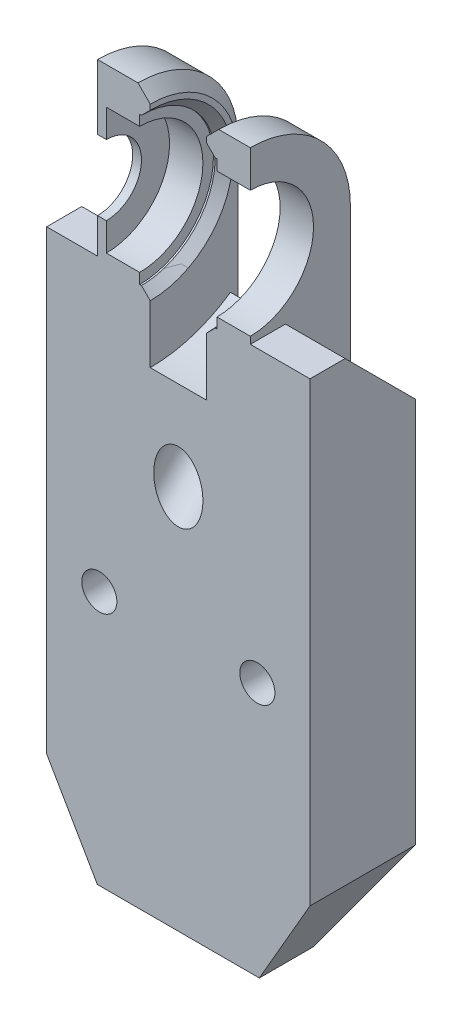
SolidWorks part; units mm, degrees
ref_plane "前视基准面" through (0, 0, 0) normal (0, 0, 1) x (1, 0, 0)
ref_plane "上视基准面" through (0, 0, 0) normal (0, 1, 0) x (1, 0, 0)
ref_plane "右视基准面" through (0, 0, 0) normal (1, 0, 0) x (0, 0, -1)
other "Configuration Table"
sketch "草图1" plane through (0, 0, 0) normal (0, 0, 1) x (1, 0, 0)
  line L1 (0, 0) -> (15, 0)
  line L2 (0, 0) -> (0, 23)
  line L3 (0, 23) -> (15, 23)
  line L4 (15, 0) -> (15, 23)
  dimension "D1" = 15
  dimension "D2" = 23
extrude "凸台-拉伸1" add sketch "草图1" along normal blind 12
ref_plane "基准面1" through (3.4, 0, 0) normal (-1, 0, 0) x (0, 0, 1)
sketch "草图2" plane through (3.4, 0, 0) normal (-1, 0, 0) x (0, 0, 1)
  line L0 (12, 23) -> (0, 23) construction
  line L1 (0.3, 23) -> (11.7, 23)
  line L2 (0.3, 23) -> (0.3, 27)
  line L4 (11.7, 23) -> (11.7, 27)
  line L5 (6, 27) -> (6, 23) construction
  arc A1 (11.7, 27) -> (0.3, 27) centre (6, 27) ccw
  circle A3 centre (6, 27) radius 3.6
  dimension "D2" = 4
  dimension "D3" = 7.2
  dimension "D1" = 11.4
extrude "凸台-拉伸2" add sketch "草图2" against normal blind 2.5
sketch "草图4" plane through (5.9, 0, 0) normal (1, 0, 0) x (0, 0, -1)
  circle A0 centre (-6, 27) radius 4.2
  circle M2 centre (-6, 27) radius 3.6
  line M6 (-11.7, 23) -> (-0.3, 23)
  dimension "D1" = 8.4
extrude "切除-拉伸1" cut sketch "草图4" against normal blind 0.6 and the other way blind 2.5 contours M2 | A0 M6 M2 | A0 M6 region at (5.9, 24.5932, 2.7023) region at (5.9, 22.9198, 6) region at (5.9, 27, 6)
chamfer "倒角1" distance 0.5 angle 45 1 edges at (5.9, 31.2, 6)
ref_plane "基准面2" through (7.5, 0, 0) normal (-1, 0, 0) x (0, 0, 1)
mirror "镜向1" about plane through (7.5, 0, 0) normal (-1, 0, 0) of "切除-拉伸1", "倒角1", "凸台-拉伸2"
sketch "草图5" plane through (7.5, 0, 0) normal (-1, 0, 0) x (0, 0, 1)
  arc A2 (2.8, 31) -> (15.2, 31) centre (9, 31) ccw
  circle A3 centre (9, 31) radius 8.2
  dimension "D1" = 2
extrude "切除-拉伸2" cut sketch "草图5" against normal mid plane 3.2 contours A3 region at (7.5, 31, 9)
sketch "草图6" plane through (3.4, 0, 0) normal (-1, 0, 0) x (0, 0, 1)
  line L3 (0.3, 27) -> (0.3, 23)
  line L4 (0.3, 23) -> (11.7, 23)
  line L5 (11.7, 23) -> (11.7, 27)
  line L6 (0.3, 27) -> (0.3, 23)
  line L7 (0.3, 23) -> (11.7, 23)
  line L8 (11.7, 23) -> (11.7, 27)
  line L9 (7, 28.7321) -> (7, 25.2679)
  circle A0 centre (6, 27) radius 3.6 construction
  arc A1 (11.7, 27) -> (0.3, 27) centre (6, 27) ccw
  arc A2 (11.7, 27) -> (0.3, 27) centre (6, 27) ccw
  circle A3 centre (6, 27) radius 3.6
  circle A6 centre (6, 27) radius 2
  point P11 (7, 27)
  circle M7 centre (6, 27) radius 3.6
  line M8 (0.3, 27) -> (0.3, 23)
  line M9 (0.3, 23) -> (11.7, 23)
  line M10 (11.7, 23) -> (11.7, 27)
  arc M11 (11.7, 27) -> (0.3, 27) centre (6, 27) ccw
  dimension "D3" = 4
  dimension "D2" = 1
  dimension "D1" = 0
extrude "凸台-拉伸3" add sketch "草图6" along normal blind 0.5 contours M11 M8 M9 M10 M7 | A6 M7 | L9 A6 region at (3.4, 32.5503, 6) region at (3.4, 27, 7.41) region at (3.4, 27, 2.5018)
sketch "草图7" plane through (0, 0, 0) normal (0, 0, -1) x (-1, 0, 0)
  line L0 (-15, 23) -> (0, 23) construction
  line L1 (-10.6, 23) -> (-4.4, 23)
  line L2 (-10.6, 23) -> (-10.6, 17.8)
  line L3 (-10.6, 17.8) -> (-4.4, 17.8)
  line L4 (-4.4, 23) -> (-4.4, 17.8)
  line L5 (-7.5, 0) -> (-7.5, 17.8) construction
  line L6 (0, 0) -> (-15, 0) construction
  dimension "D1" = 6.2
  dimension "D2" = 5.2
chamfer "倒角2" distance 4 angle 45 1 edges at (7.5, 23, 0)
ref_plane "基准面3" through (7.5, 0, 0) normal (-1, 0, 0) x (0, 0, 1)
sketch "草图15" plane through (7.5, 0, 0) normal (-1, 0, 0) x (0, 0, 1)
  line L0 (0.4645, 19.4645) -> (7.4645, 12.4645)
  line L1 (4, 23) -> (0, 19) construction
  line L2 (12, 11) -> (11, 11)
  line L3 (12, 0) -> (0, 0) construction
  line L4 (12, 23) -> (12, 0) construction
  line L5 (12, 23) -> (12, 0) construction
  arc A0 (11, 11) -> (7.4645, 12.4645) centre (11, 16) cw
  dimension "D2" = 11
  dimension "D1" = 5
  dimension "D3" = 1
sketch "草图40" plane through (0, 0, 12) normal (0, 0, 1) x (1, 0, 0)
  line L0 (5.9, 26) -> (5.9, 23)
  line L1 (15, 23) -> (0, 23) construction
  line L2 (5.9, 23) -> (5.9, 27) construction
  line L3 (5.9, 23) -> (0, 23)
  line L4 (0, 23) -> (2.9, 26)
  line L5 (2.9, 26) -> (5.9, 26)
  line L6 (2.9, 23) -> (2.9, 27) construction
  line L7 (5.9, 27) -> (2.9, 27) construction
  dimension "D1" = 1
extrude "凸台-拉伸4" add sketch "草图40" against normal up to surface (0.3 mm away) up to face at (4.4, 25, 11.7)
sketch "草图41" plane through (0, 0, 0) normal (-1, 0, 0) x (0, 0, 1)
  line L0 (11.7, 26) -> (7.85, 23)
  line L1 (11.7, 23) -> (4, 23) construction
  line L4 (11.7, 26) -> (11.7, 23)
  line L5 (11.7, 23) -> (12, 23)
  line L6 (12, 23) -> (12, 26)
  line L7 (12, 26) -> (11.7, 26)
  line L8 (11.7, 26) -> (11.7, 23)
  line L9 (11.7, 23) -> (12, 23)
  line L10 (12, 23) -> (12, 26)
  line L11 (12, 26) -> (11.7, 26)
  line M7 (12, 23) -> (11.7, 23)
  line M8 (11.7, 23) -> (4, 23)
  dimension "D1" = 0
extrude "凸台-拉伸5" add sketch "草图41" against normal blind 2.9 contours L8 L0 M8 | L10 L11 L8 M7 region at (0, 24, 10.4167) region at (0, 24.5, 11.85)
mirror "镜向3" about plane through (7.5, 0, 0) normal (-1, 0, 0) of "凸台-拉伸4", "凸台-拉伸5"
sketch "草图57" plane through (0, 0, 0) normal (0, 0, -1) x (-1, 0, 0)
  line L0 (-15, 6.5) -> (0, 6.5) construction
  line L1 (-15, 9.5) -> (0, 9.5) construction
  line L2 (-7.5, 17.8076) -> (-7.5, 0) construction
  line L5 (0, 19) -> (-15, 19)
  line L6 (-15, 19) -> (-15, 0)
  line L7 (-15, 0) -> (0, 0)
  line L8 (0, 0) -> (0, 19)
  line L10 (0, 19) -> (-15, 19)
  line L11 (-15, 19) -> (-15, 0)
  line L12 (-15, 0) -> (0, 0)
  line L13 (0, 0) -> (0, 19)
  circle A0 centre (-12, 6.5) radius 1.7
  circle A1 centre (-3, 6.5) radius 1.7
  dimension "D2" = 3
  dimension "D3" = 3.4
  dimension "D4" = 3
  dimension "D1" = 0
extrude "切除-拉伸3" cut sketch "草图57" against normal blind 2 contours A0 | A1 region at (12, 6.5, 0) region at (3, 6.5, 0)
sketch "草图58" plane through (0, 0, 2) normal (0, 0, -1) x (-1, 0, 0)
  circle A0 centre (-12, 6.5) radius 1
  circle A1 centre (-3, 6.5) radius 1
  dimension "D1" = 2
extrude "切除-拉伸4" cut sketch "草图58" against normal up to next
sketch "草图59" plane through (0, 0, 12) normal (0, 0, 1) x (1, 0, 0)
  line L0 (15, 0) -> (15, 26) construction
  line L1 (3, 4.537) -> (4.7, 5.5185)
  line L2 (4.7, 5.5185) -> (4.7, 7.4815)
  line L3 (4.7, 7.4815) -> (3, 8.463)
  line L4 (3, 8.463) -> (1.3, 7.4815)
  line L5 (1.3, 7.4815) -> (1.3, 5.5185)
  line L6 (1.3, 5.5185) -> (3, 4.537)
  line L7 (12, 4.537) -> (13.7, 5.5185)
  line L8 (13.7, 5.5185) -> (13.7, 7.4815)
  line L9 (13.7, 7.4815) -> (12, 8.463)
  line L10 (12, 8.463) -> (10.3, 7.4815)
  line L11 (10.3, 7.4815) -> (10.3, 5.5185)
  line L12 (10.3, 5.5185) -> (12, 4.537)
  circle A0 centre (3, 6.5) radius 1.7 construction
  circle A1 centre (12, 6.5) radius 1.7 construction
  dimension "D1" = 3.4
extrude "切除-拉伸5" cut sketch "草图59" against normal blind 2 contours L2 L3 L4 L5 L6 L1 | L12 L7 L8 L9 L10 L11
sweep "切除-扫描1" cut path "草图15" circular profile diameter 2.8 parameters "D3"=2.8
sketch "草图79" plane through (7.5, 0, 0) normal (-1, 0, 0) x (0, 0, 1)
  arc A1 (-0.1177, 28.0068) -> (12.1941, 27.2693) centre (6, 27) ccw
  circle A2 centre (6, 27) radius 8
  dimension "D1" = 1.8
extrude "切除-拉伸7" cut sketch "草图79" against normal mid plane 3.2 contours A2 region at (7.5, 27, 6)
sketch "草图78" plane through (0, 0, 0) normal (-1, 0, 0) x (0, 0, 1)
  line L0 (6, 0) -> (6, 33.9991)
  line L1 (12, 0) -> (0, 0)
  line L2 (12, 0) -> (12, 33.9991)
  line L3 (12, 33.9991) -> (0, 33.9991)
  line L4 (0, 0) -> (0, 33.9991)
  line M1 (11.7, 26) -> (7.85, 23)
  line M2 (7.85, 23) -> (4, 23)
  line M5 (0, 0) -> (12, 0)
  line M6 (12, 0) -> (12, 26)
  line M7 (12, 26) -> (11.7, 26)
extrude "切除-拉伸6" cut sketch "草图78" against normal through all contours L0 M5 M6 M7 M1 M2 | L2 L3 L0 M2 M1 M7 region at (0, 12.0798, 9.0743) region at (0, 28.9983, 8.8188)
chamfer "倒角4" distance 0.7 angle 45 4 edges at (9.1, 23.15, 0.3) (9.1, 31.0305, 1.9695) (5.9, 31.0305, 1.9695) (5.9, 23.15, 0.3)
chamfer "倒角5" distance 0.5 angle 45 2 edges at (9.1, 22.8503, 5.3519) (5.9, 22.8503, 5.3519)
sketch "草图80" plane through (0, 0, 0) normal (0, -1, 0) x (1, 0, 0)
  line L4 (15, 6) -> (0, 6)
  line L5 (0, 6) -> (0, 0)
  line L6 (0, 0) -> (15, 0)
  line L7 (15, 0) -> (15, 6)
  line L8 (15, 6) -> (0, 6)
  line L9 (0, 6) -> (0, 0)
  line L10 (0, 0) -> (15, 0)
  line L11 (15, 0) -> (15, 6)
  dimension "D1" = 0
extrude "凸台-拉伸7" add sketch "草图80" along normal blind 8
chamfer "倒角6" distance 5 angle 30 3 edges at (15, -8, 3) (7.5, -8, 0) (0, -8, 3) first distance on face at (15, 9.8, 3.2) first distance on face at (7.5, 9.8248, 0) first distance on face at (0, 9.8, 3.2)
